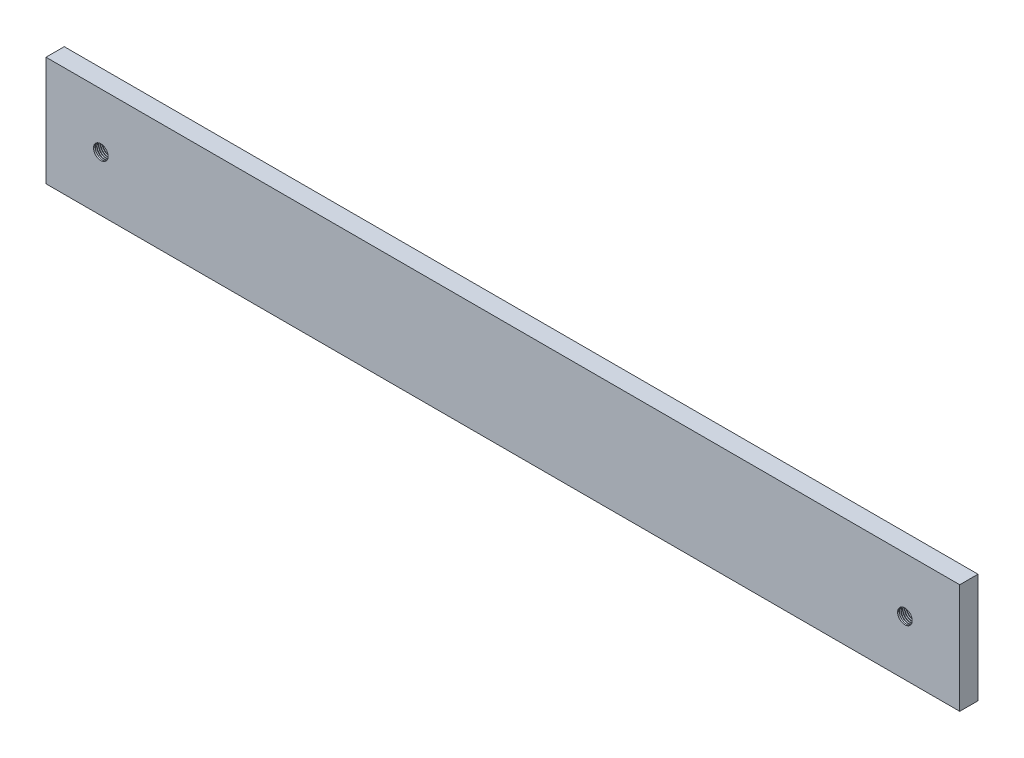
SolidWorks part; units mm, degrees
ref_plane "Płaszczyzna przednia" through (0, 0, 0) normal (0, 0, 1) x (1, 0, 0)
ref_plane "Płaszczyzna górna" through (0, 0, 0) normal (0, 1, 0) x (1, 0, 0)
ref_plane "Płaszczyzna prawa" through (0, 0, 0) normal (1, 0, 0) x (0, 0, -1)
sketch "Szkic1" plane through (0, 0, 0) normal (0, 1, 0) x (1, 0, 0)
  line L1 (-241.0691, 0) -> (258.9309, 0)
  line L2 (-241.0691, 0) -> (-241.0691, 10)
  line L3 (-241.0691, 10) -> (258.9309, 10)
  line L4 (258.9309, 0) -> (258.9309, 10)
  dimension "D1" = 500
  dimension "D2" = 10
extrude "Dodanie-wyciągnięcie1" add sketch "Szkic1" along normal blind 60
hole_wizard "Otwory ustalające Ø8.0mm2" positions "Szkic7" profile "Szkic8" hole size "Ø8.0" standard "Ansi Metric" end condition through all
sketch "Szkic7" plane through (0, 0, -10) normal (0, 0, -1) x (-1, 0, 0)
  line L0 (-258.9309, 60) -> (241.0691, 60) construction
  line L1 (241.0691, 60) -> (241.0691, 0) construction
  line L2 (-258.9309, 60) -> (-258.9309, 0) construction
  point P0 (211.0691, 30)
  point P2 (-228.9309, 30)
  dimension "D1" = 30
  dimension "D2" = 30
  dimension "D3" = 30
  dimension "D4" = 30
sketch "Szkic8" plane through (-211.0691, 30, -10) normal (1, 0, 0) x (0, 1, 0)
  line L0 (0, 0) -> (0, 10)
  line L1 (0, 10) -> (4, 10)
  line L2 (4, 10) -> (4, 0.025)
  line L3 (4, 0.025) -> (4.025, 0)
  line L5 (4.025, 0) -> (0, 0)
  line L6 (-4, 0.025) -> (-4.025, 0) construction
  line L11 (0, -6.35) -> (0, 107.95) construction
  dimension "Œrednica otworu na wylot" = 8
  dimension "G³êbokoœæ otworu na wylot" = 10
  dimension "Œrednica zewnêtrznego pog³êbienia sto¿kowego" = 8.05
  dimension "K¹t zewnêtrznego pog³êbienia sto¿kowego" = 90
thread "Gwint1" pitch 1 method cut profile "Profil gwintu1" start angle 0, offset 0, length 0, pitch 1, diameter 8
ref_plane "Płaszczyzna1" through (224.9309, 30, 0) normal (0, -1, 0) x (-1, 0, 0)
sketch "Profil gwintu1" plane through (224.9309, 30, 0) normal (0, -1, 0) x (-1, 0, 0)
  line L0 (0, 0) -> (0, 1) construction
  line L1 (0, 0) -> (0.5413, 0.3125)
  line L2 (0.5413, 0.3125) -> (0.5413, 0.4375)
  line L3 (0.5413, 0.4375) -> (0, 0.75)
  line L4 (0.5413, 0.375) -> (0, 0.375) construction
  line L11 (0, 0) -> (0, 0.75)
  point P2 (0, 0)
  dimension "Pitch" = 1
  dimension "Profile_Angle" = 60
  dimension "Profile_Land" = 0.125
  dimension "Profile_Height" = 0.5413
thread "Gwint2" pitch 1 method cut profile "Profil gwintu2" start angle 0, offset 0, length 0, pitch 1, diameter 8
ref_plane "Płaszczyzna2" through (-215.0691, 30, 0) normal (0, -1, 0) x (-1, 0, 0)
sketch "Profil gwintu2" plane through (-215.0691, 30, 0) normal (0, -1, 0) x (-1, 0, 0)
  line L0 (0, 0) -> (0, 1) construction
  line L1 (0, 0) -> (0.5413, 0.3125)
  line L2 (0.5413, 0.3125) -> (0.5413, 0.4375)
  line L3 (0.5413, 0.4375) -> (0, 0.75)
  line L4 (0.5413, 0.375) -> (0, 0.375) construction
  line L11 (0, 0) -> (0, 0.75)
  point P2 (0, 0)
  dimension "Pitch" = 1
  dimension "Profile_Angle" = 60
  dimension "Profile_Land" = 0.125
  dimension "Profile_Height" = 0.5413
